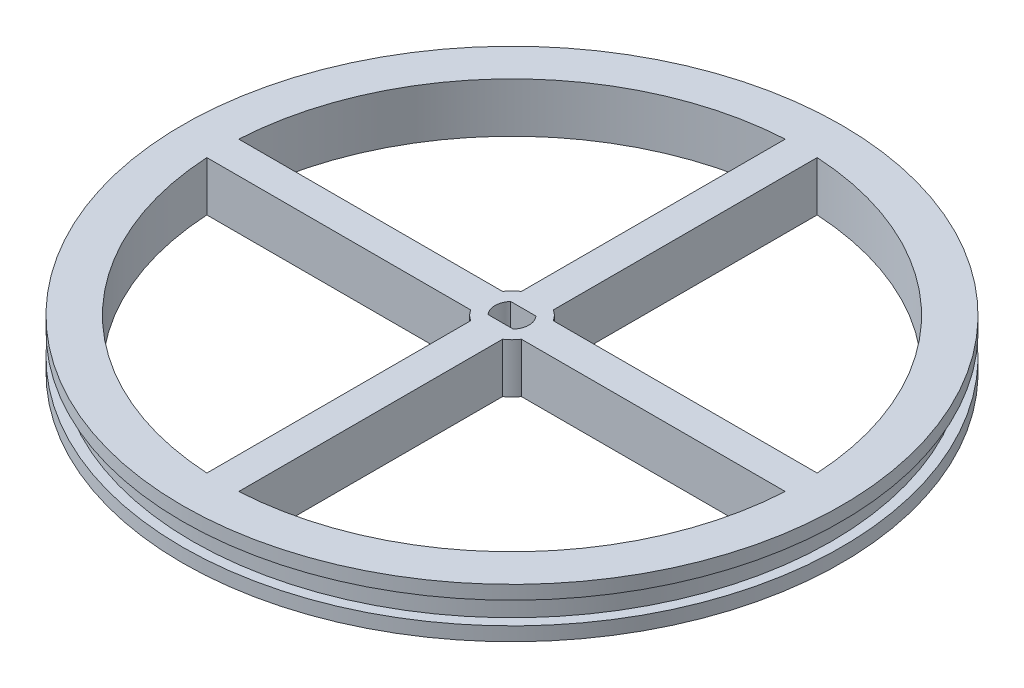
SolidWorks part; units mm, degrees
ref_plane "Front Plane" through (0, 0, 0) normal (0, 0, 1) x (1, 0, 0)
ref_plane "Top Plane" through (0, 0, 0) normal (0, 1, 0) x (1, 0, 0)
ref_plane "Right Plane" through (0, 0, 0) normal (1, 0, 0) x (0, 0, -1)
sketch "Sketch1" plane through (0, 0, 0) normal (0, 1, 0) x (1, 0, 0)
  line L0 (-2.0125, 1.8) -> (2.0125, 1.8)
  line L1 (-2.0125, -1.8) -> (2.0125, -1.8)
  line L2 (-2.54, 4.0286) -> (-2.54, 45.9674)
  line L3 (2.54, 4.0286) -> (2.54, 45.9674)
  line L4 (0, 0) -> (0, 46.0375) construction
  line L5 (4.0286, 2.54) -> (45.9674, 2.54)
  line L6 (4.0286, -2.54) -> (45.9674, -2.54)
  line L7 (2.54, -4.0286) -> (2.54, -45.9674)
  line L8 (-2.54, -4.0286) -> (-2.54, -45.9674)
  line L9 (-4.0286, -2.54) -> (-45.9674, -2.54)
  line L10 (-4.0286, 2.54) -> (-45.9674, 2.54)
  line L11 (0, 0) -> (2.54, 4.0286) construction
  line L12 (0, 0) -> (4.0286, -2.54) construction
  circle A0 centre (0, 0) radius 52.3875
  arc A1 (-2.54, 45.9674) -> (-45.9674, 2.54) centre (0, 0) ccw
  arc A2 (-4.0286, -2.54) -> (-2.54, -4.0286) centre (0, 0) ccw
  arc A3 (-2.0125, 1.8) -> (-2.0125, -1.8) centre (0, 0) ccw
  arc A4 (2.0125, -1.8) -> (2.0125, 1.8) centre (0, 0) ccw
  arc A5 (-45.9674, -2.54) -> (-2.54, -45.9674) centre (0, 0) ccw
  arc A6 (45.9674, 2.54) -> (2.54, 45.9674) centre (0, 0) ccw
  arc A7 (2.54, -45.9674) -> (45.9674, -2.54) centre (0, 0) ccw
  arc A8 (2.54, -4.0286) -> (4.0286, -2.54) centre (0, 0) ccw
  arc A9 (4.0286, 2.54) -> (2.54, 4.0286) centre (0, 0) ccw
  arc A10 (-2.54, 4.0286) -> (-4.0286, 2.54) centre (0, 0) ccw
  circle A11 centre (0, 0) radius 50.8
  dimension "D1" = 104.775
  dimension "D2" = 6.35
  dimension "D3" = 9.525
  dimension "D4" = 5.4
  dimension "D9" = 101.6
  dimension "D5" = 3.6
  dimension "D6" = 5.08
  dimension "D8" = 90
  dimension "D7" = 4
extrude "Boss-Extrude1" add sketch "Sketch1" along normal blind 7.9 contours A11 L2 A10 L10 A1 L5 A9 L3 A6 L7 A8 L6 A7 A4 L1 A3 L0 A5 L9 A2 L8 | A0 A11 region at (-50.9058, 0, 0) region at (-49.3632, 0, 0)
ref_plane "Plane1" through (0, 3.95, 0) normal (0, 1, 0) x (1, 0, 0)
extrude "Cut-Extrude1" cut sketch "Sketch1<3>" against normal mid plane 3.5306 from surface contours A0 A11 region at (-50.9058, 0, 0) starting at plane "Plane1"
sketch "Sketch1<3>" plane through (0, 0, 0) normal (0, 1, 0) x (1, 0, 0) same geometry as "Sketch1"
